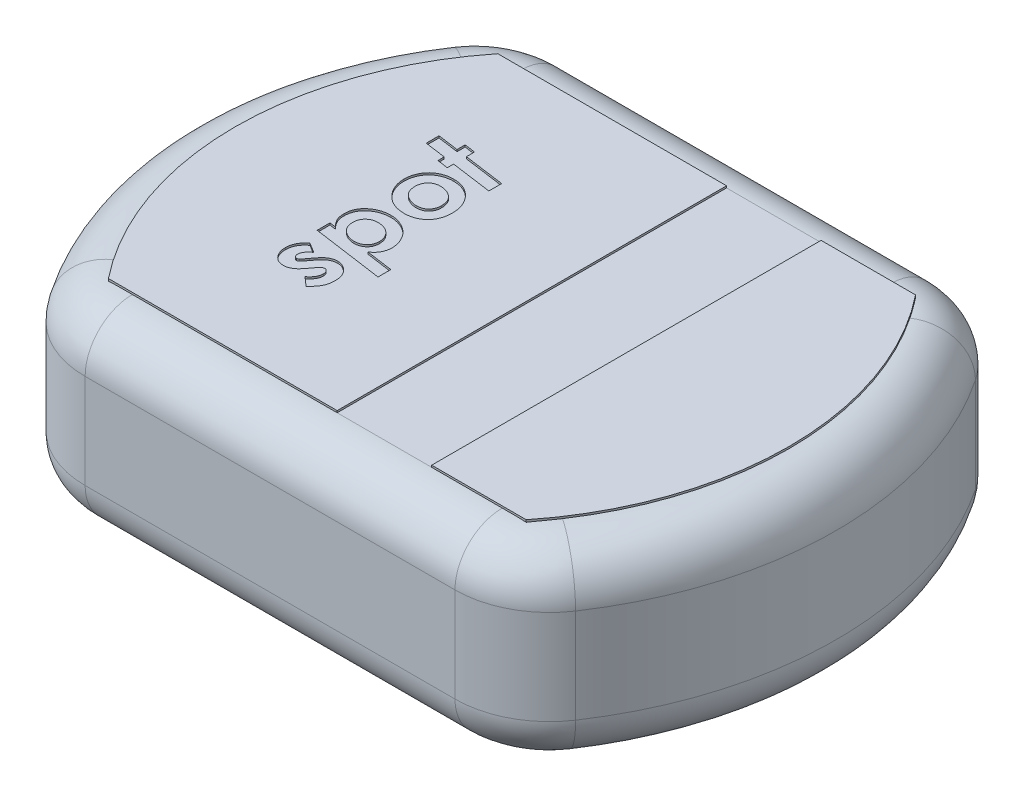
SolidWorks part; units mm, degrees
ref_plane "Front Plane" through (0, 0, 0) normal (0, 0, 1) x (1, 0, 0)
ref_plane "Top Plane" through (0, 0, 0) normal (0, 1, 0) x (1, 0, 0)
ref_plane "Right Plane" through (0, 0, 0) normal (1, 0, 0) x (0, 0, -1)
sketch "Sketch1" plane through (0, 0, 0) normal (0, 1, 0) x (1, 0, 0)
  line L0 (-31, 0) -> (31, 0) construction
  line L1 (-43.561, -32.512) -> (43.561, -32.512) construction
  line L2 (-43.561, -32.512) -> (-43.561, 32.512) construction
  line L3 (-43.561, 32.512) -> (43.561, 32.512) construction
  line L4 (43.561, -32.512) -> (43.561, 32.512) construction
  line L5 (-43.561, -32.512) -> (43.561, 32.512) construction
  line L6 (-43.561, 32.512) -> (43.561, -32.512) construction
  line L7 (-31, -32.512) -> (-31, 32.512) construction
  line L8 (31, -32.512) -> (31, 32.512) construction
  line L9 (-31, 32.512) -> (31, 32.512)
  line L10 (31, -32.512) -> (-31, -32.512)
  arc A0 (31, 32.512) -> (31, -32.512) centre (-4.7954, 0) cw
  arc A1 (-31, 32.512) -> (-31, -32.512) centre (4.7954, 0) ccw
  point P0 (0, 0)
  point P11 (-31, 0)
  point P14 (31, 0)
  point P15 (0, 0)
  dimension "D1" = 87.122
  dimension "D2" = 65.024
  dimension "D3" = 62
extrude "Boss-Extrude1" add sketch "Sketch1" along normal blind 25.4
sketch "Sketch2" plane through (0, 25.4, 0) normal (0, 1, 0) x (1, 0, 0)
  line L4 (-28.0693, -26.162) -> (28.0693, -26.162)
  line L5 (28.0693, 26.162) -> (-28.0693, 26.162)
  line L6 (-28.0693, -26.162) -> (28.0693, -26.162)
  line L7 (28.0693, 26.162) -> (-28.0693, 26.162)
  arc A4 (-28.0693, 26.162) -> (-28.0693, -26.162) centre (4.7954, 0) ccw
  arc A5 (28.0693, -26.162) -> (28.0693, 26.162) centre (-4.7954, 0) ccw
  arc A6 (-28.0693, 26.162) -> (-28.0693, -26.162) centre (4.7954, 0) ccw
  arc A7 (28.0693, -26.162) -> (28.0693, 26.162) centre (-4.7954, 0) ccw
  dimension "D1" = 6.35
extrude "Boss-Extrude2" add sketch "Sketch2" along normal blind 0.254
fillet "Fillet1" radius 12.7 4 edges at (-31, 12.7, -32.512) (31, 12.7, -32.512) (31, 12.7, 32.512) (-31, 12.7, 32.512)
fillet "Fillet2" radius 6.35 16 edges at (-30.8365, 0, 31.0126) (-43.561, 0, 0) (-30.8365, 0, -31.0126) (0, 0, -32.512) (30.8365, 0, -31.0126) (43.561, 0, 0) (30.8365, 0, 31.0126) (-30.8365, 25.4, 31.0126) (-43.561, 25.4, 0) (-30.8365, 25.4, -31.0126) (0, 25.4, -32.512) (30.8365, 25.4, -31.0126) (43.561, 25.4, 0) (30.8365, 25.4, 31.0126) (0, 0, 32.512) (0, 25.4, 32.512)
sketch "Sketch3" plane through (0, 25.654, 0) normal (0, 1, 0) x (1, 0, 0)
  line L0 (28.0693, 26.162) -> (-28.0693, 26.162) construction
  line L1 (15.3693, -26.162) -> (2.6693, -26.162)
  line L2 (15.3693, -26.162) -> (15.3693, 26.162)
  line L3 (15.3693, 26.162) -> (2.6693, 26.162)
  line L4 (2.6693, -26.162) -> (2.6693, 26.162)
  line L5 (15.3693, -26.162) -> (2.6693, 26.162) construction
  line L6 (15.3693, 26.162) -> (2.6693, -26.162) construction
  line L7 (-28.0693, -26.162) -> (28.0693, -26.162) construction
  point P0 (9.0193, 0)
  point P7 (17.2621, -26.162)
  dimension "D1" = 12.7
  dimension "D2" = 12.7
extrude "Cut-Extrude3" cut sketch "Sketch3" against normal blind 0.254
sketch "Sketch4" plane through (0, 25.654, 0) normal (0, 1, 0) x (1, 0, 0)
  line L0 (-12.7, -26.162) -> (-12.7, 26.162) construction
  line L1 (-28.0693, -26.162) -> (2.6693, -26.162) construction
  line L2 (2.6693, 26.162) -> (-28.0693, 26.162) construction
  text T0 "<b><i>spot</i></b>" font "Century Gothic" height in points 36
  point P6 (-12.7, -26.162)
extrude "Cut-Extrude4" cut sketch "Sketch4" against normal blind 0.254
